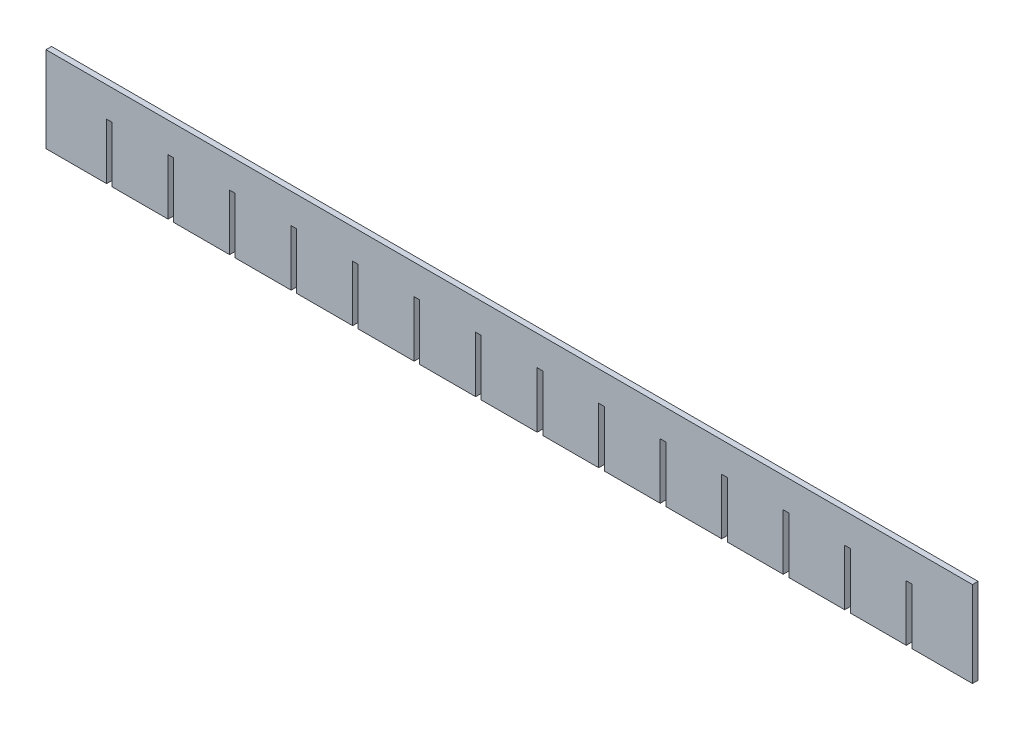
SolidWorks part; units mm, degrees
ref_plane "Ebene vorne" through (0, 0, 0) normal (0, 0, 1) x (1, 0, 0)
ref_plane "Ebene oben" through (0, 0, 0) normal (0, 1, 0) x (1, 0, 0)
ref_plane "Ebene rechts" through (0, 0, 0) normal (1, 0, 0) x (0, 0, -1)
sketch "Sketch1" plane through (0, 0, 0) normal (0, 0, 1) x (1, 0, 0)
  line L1 (-248.5, -23) -> (248.5, -23)
  line L2 (-248.5, -23) -> (-248.5, 23)
  line L3 (-248.5, 23) -> (248.5, 23)
  line L4 (248.5, -23) -> (248.5, 23)
  line L5 (-248.5, -23) -> (248.5, 23) construction
  line L6 (-248.5, 23) -> (248.5, -23) construction
  point P0 (0, 0)
  dimension "D1" = 46
  dimension "D2" = 497
extrude "Boss-Extrude1" add sketch "Sketch1" along normal blind 3
sketch "Sketch2" plane through (0, 0, 3) normal (0, 0, 1) x (1, 0, 0)
  line L6 (-248.5, -23) -> (-216, -23)
  line L7 (-248.5, -23) -> (248.5, -23) construction
  line L8 (-216, -23) -> (-216, 7)
  line L9 (-216, 7) -> (-213, 7)
  line L10 (-213, 7) -> (-213, -23)
  line L11 (-216, -23) -> (-213, -23)
  point P4 (-214.5, -23)
  dimension "D1" = 34
  dimension "D2" = 30
  dimension "D3" = 3
extrude "Cut-Extrude1" cut sketch "Sketch2" against normal through all contours L11 L10 L9 L8
pattern_linear "LPattern1" count 14 spacing 33 along (1, 0, 0) of "Cut-Extrude1"
